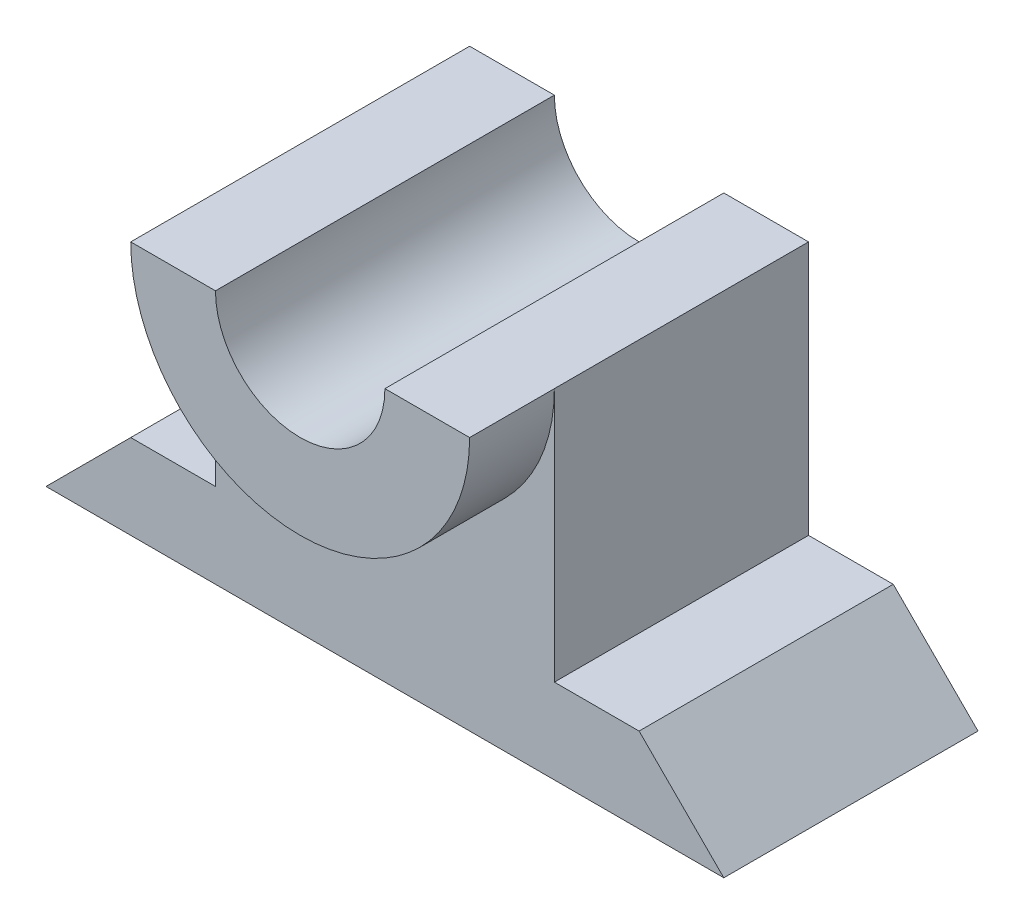
SolidWorks part; units mm, degrees
ref_plane "前基準面" through (0, 0, 0) normal (0, 0, 1) x (1, 0, 0)
ref_plane "上基準面" through (0, 0, 0) normal (0, 1, 0) x (1, 0, 0)
ref_plane "右基準面" through (0, 0, 0) normal (1, 0, 0) x (0, 0, -1)
sketch "草圖1" plane through (0, 0, 0) normal (0, 0, 1) x (1, 0, 0)
  line L0 (0, 19.53) -> (0, -19.53) construction
  line L1 (0, 0) -> (20, 0)
  line L2 (20, 0) -> (15, 5)
  line L3 (15, 5) -> (10, 5)
  line L4 (10, 5) -> (10, 20)
  line L5 (10, 20) -> (0, 20)
  line L6 (0, 20) -> (0, 0)
  point P4 (0, 0)
  point P7 (0, 0)
  point P12 (0, 0)
  dimension "D1" = 20
  dimension "D2" = 5
  dimension "D3" = 5
  dimension "D4" = 20
  dimension "D5" = 10
extrude "填料-伸長1" add sketch "草圖1" along normal blind 15
sketch "草圖2" plane through (0, 0, 0) normal (0, 0, 1) x (1, 0, 0)
  line L0 (0, 0) -> (0, 20) construction
  line L1 (10, 20) -> (0, 20)
  line L2 (0, 20) -> (0, 10)
  arc A0 (0, 15) -> (5, 20) centre (0, 20) ccw
  arc A1 (0, 10) -> (10, 20) centre (0, 20) ccw
  dimension "D1" = 10
extrude "填料-伸長2" add sketch "草圖2" along normal blind 20 contours L2 A1 L1 A0 region at (4.9515, 15.0485, 0)
extrude "除料-伸長1" cut sketch "草圖2<3>" along normal blind 20 contours L2 A0 L1 region at (2.1221, 17.8779, 0)
sketch "草圖2<3>" plane through (0, 0, 0) normal (0, 0, 1) x (1, 0, 0) same geometry as "草圖2"
mirror "鏡射1" about plane through (0, 0, 0) normal (1, 0, 0) of "除料-伸長1", "填料-伸長2", "填料-伸長1"
